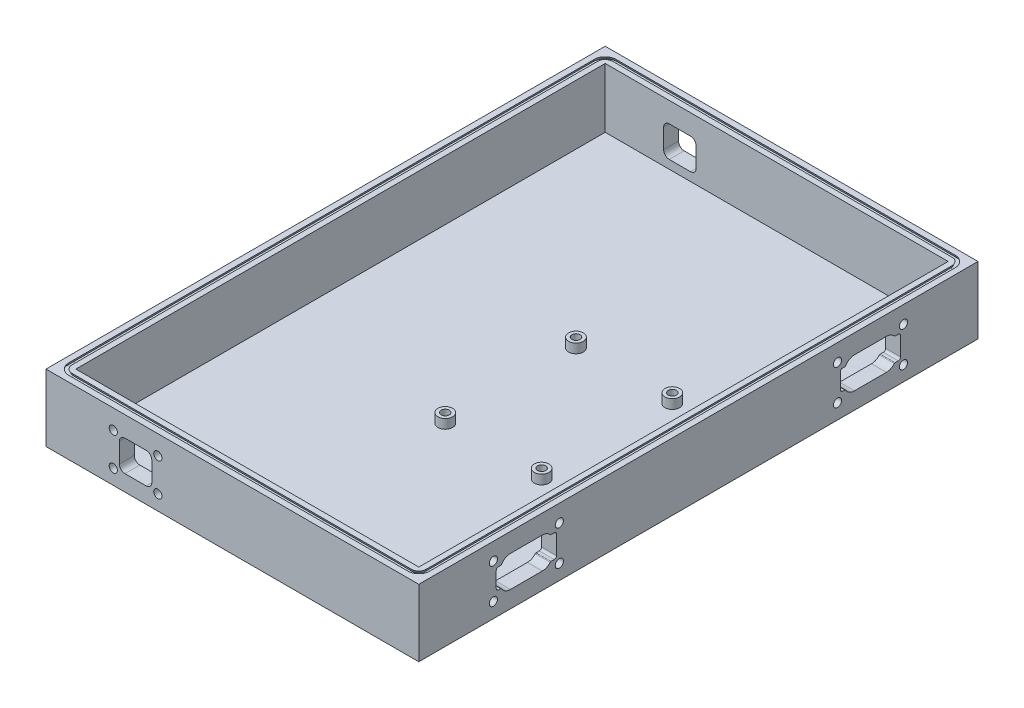
SolidWorks part; units mm, degrees
ref_plane "Front Plane" through (0, 0, 0) normal (0, 0, 1) x (1, 0, 0)
ref_plane "Top Plane" through (0, 0, 0) normal (0, 1, 0) x (1, 0, 0)
ref_plane "Right Plane" through (0, 0, 0) normal (1, 0, 0) x (0, 0, -1)
sketch "Sketch1" plane through (0, 0, 0) normal (0, 1, 0) x (1, 0, 0)
  line L1 (0, 0) -> (254, 0)
  line L2 (0, 0) -> (0, 381)
  line L3 (0, 381) -> (254, 381)
  line L4 (254, 0) -> (254, 381)
  dimension "D1" = 254
  dimension "D2" = 381
extrude "Boss-Extrude1" add sketch "Sketch1" along normal blind 45.72
sketch "12 pin hole" [suppressed] plane through (254, 0, 0) normal (1, 0, 0) x (0, 0, -1)
  line L8 (50.8, 10.16) -> (95.758, 10.16) construction
  line L9 (50.8, 10.16) -> (50.8, 34.036) construction
  line L10 (50.8, 34.036) -> (95.758, 34.036) construction
  line L11 (95.758, 10.16) -> (95.758, 34.036) construction
  line L12 (55.7357, 28.956) -> (54.2925, 28.956)
  line L13 (52.7685, 27.432) -> (52.7685, 16.764)
  line L14 (54.2925, 15.24) -> (55.7357, 15.24)
  line L16 (90.087, 29.972) -> (92.2655, 29.972)
  line L17 (93.7895, 28.448) -> (93.7895, 15.748)
  line L18 (92.2655, 14.224) -> (90.087, 14.224)
  line L21 (62.4205, 25.654) -> (84.1375, 25.654) construction
  line L22 (62.4205, 25.654) -> (62.4205, 18.542) construction
  line L23 (62.4205, 18.542) -> (84.1375, 18.542) construction
  line L24 (84.1375, 25.654) -> (84.1375, 18.542) construction
  line L25 (62.4205, 32.7152) -> (84.1375, 32.7152)
  line L26 (62.4205, 11.4808) -> (84.1375, 11.4808)
  line L27 (52.7685, 22.098) -> (50.8, 22.098) construction
  line L28 (93.7895, 22.098) -> (95.758, 22.098) construction
  arc A4 (62.4205, 32.7152) -> (56.3868, 29.3222) centre (62.4205, 25.654) ccw
  arc A5 (89.5075, 30.2392) -> (84.1375, 32.7152) centre (84.1375, 25.654) ccw
  arc A6 (62.4205, 11.4808) -> (56.3868, 14.8738) centre (62.4205, 18.542) cw
  arc A7 (89.5075, 13.9568) -> (84.1375, 11.4808) centre (84.1375, 18.542) cw
  arc A8 (90.087, 29.972) -> (89.5075, 30.2392) centre (90.087, 30.734) cw
  arc A9 (90.087, 14.224) -> (89.5075, 13.9568) centre (90.087, 13.462) ccw
  arc A10 (55.7357, 15.24) -> (56.3868, 14.8738) centre (55.7357, 14.478) cw
  arc A11 (55.7357, 28.956) -> (56.3868, 29.3222) centre (55.7357, 29.718) ccw
  arc A12 (92.2655, 29.972) -> (93.7895, 28.448) centre (92.2655, 28.448) cw
  arc A13 (93.7895, 15.748) -> (92.2655, 14.224) centre (92.2655, 15.748) cw
  arc A14 (52.7685, 16.764) -> (54.2925, 15.24) centre (54.2925, 16.764) ccw
  arc A15 (54.2925, 28.956) -> (52.7685, 27.432) centre (54.2925, 27.432) ccw
  point P25 (50.8, 22.098)
  point P28 (52.7685, 22.098)
  point P29 (93.7895, 22.098)
  point P34 (62.4205, 22.098)
  point P35 (84.1375, 22.098)
  point P44 (73.279, 10.16)
  point P46 (73.279, 11.4808)
  point P59 (93.7895, 29.972)
  point P62 (93.7895, 14.224)
  point P65 (52.7685, 15.24)
  point P68 (52.7685, 28.956)
  dimension "D4" = 41.021
  dimension "D5" = 15.748
  dimension "D11" = 7.0612
  dimension "D12" = 0.762
  dimension "D13" = 1.524
  dimension "D1" = 44.958
  dimension "D2" = 23.876
  dimension "D8" = 13.716
  dimension "D9" = 21.2344
  dimension "D10" = 21.717
sketch "Sketch2" plane through (0, 45.72, 0) normal (0, 1, 0) x (1, 0, 0)
  line L0 (0, 381) -> (0, 0) construction
  line L1 (10.16, 10.16) -> (243.84, 10.16)
  line L2 (10.16, 10.16) -> (10.16, 370.84)
  line L3 (10.16, 370.84) -> (243.84, 370.84)
  line L4 (243.84, 10.16) -> (243.84, 370.84)
  line L5 (254, 381) -> (0, 381) construction
  line L6 (254, 0) -> (254, 381) construction
  line L7 (0, 0) -> (254, 0) construction
  dimension "D1" = 10.16
  dimension "D2" = 10.16
  dimension "D3" = 10.16
  dimension "D4" = 10.16
extrude "Cut-Extrude1" cut sketch "Sketch2" against normal blind 40.64
ref_plane "Plane1" through (0, 45.72, 0) normal (0, 1, 0) x (1, 0, 0)
sketch "Sketch3" plane through (0, 45.72, 0) normal (0, 1, 0) x (1, 0, 0)
  line L4 (6.35, 11.43) -> (6.35, 369.57)
  line L5 (243.84, 370.84) -> (10.16, 370.84) construction
  line L6 (10.16, 370.84) -> (10.16, 10.16) construction
  line L7 (243.84, 10.16) -> (243.84, 370.84) construction
  line L8 (10.16, 10.16) -> (243.84, 10.16) construction
  line L13 (11.43, 374.65) -> (242.57, 374.65)
  line L14 (247.65, 369.57) -> (247.65, 11.43)
  line L15 (242.57, 6.35) -> (11.43, 6.35)
  arc A0 (6.35, 369.57) -> (11.43, 374.65) centre (11.43, 369.57) cw
  arc A1 (242.57, 374.65) -> (247.65, 369.57) centre (242.57, 369.57) cw
  arc A2 (247.65, 11.43) -> (242.57, 6.35) centre (242.57, 11.43) cw
  arc A3 (11.43, 6.35) -> (6.35, 11.43) centre (11.43, 11.43) cw
  dimension "D5" = 5.08
  dimension "D1" = 3.81
  dimension "D2" = 3.81
  dimension "D3" = 3.81
  dimension "D4" = 3.81
ref_plane "Plane2" through (0, 0, 0) normal (0, 0, 1) x (1, 0, 0)
ref_plane "Plane3" through (0, 0, -15.24) normal (0, 0, 1) x (1, 0, 0)
sketch "Sketch4" plane through (0, 0, -15.24) normal (0, 0, 1) x (1, 0, 0)
  line L0 (4.064, 45.72) -> (3.2724, 43.942)
  line L1 (6.35, 45.72) -> (7.1416, 43.942)
  line L2 (3.2724, 43.942) -> (7.1416, 43.942)
  line L5 (4.064, 45.72) -> (6.35, 45.72)
  dimension "D1" = 1.778
  dimension "D2" = 2.286
  dimension "D3" = 66
  dimension "D4" = 66
sweep "Cut-Sweep2" cut profiles "Sketch4" path "Sketch3"
sketch "Sketch13" plane through (254, 0, 0) normal (1, 0, 0) x (0, 0, -1)
  line L0 (50.8, 10.16) -> (50.8, 0) construction
  line L1 (0, 0) -> (381, 0) construction
  line L2 (50.8, 10.16) -> (0, 10.16) construction
  line L3 (0, 45.72) -> (0, 0) construction
  line L4 (330.2, 0) -> (330.2, 10.16) construction
  line L5 (330.2, 10.16) -> (381, 10.16) construction
  line L6 (381, 45.72) -> (381, 0) construction
  line B0 (50.8, 10.16) -> (95.758, 10.16) construction
  line B1 (50.8, 10.16) -> (50.8, 34.036) construction
  line B2 (50.8, 34.036) -> (95.758, 34.036) construction
  line B3 (95.758, 10.16) -> (95.758, 34.036) construction
  line B4 (55.7357, 28.956) -> (54.2925, 28.956)
  line B5 (52.7685, 27.432) -> (52.7685, 16.764)
  line B6 (54.2925, 15.24) -> (55.7357, 15.24)
  line B7 (90.087, 29.972) -> (92.2655, 29.972)
  line B8 (93.7895, 28.448) -> (93.7895, 15.748)
  line B9 (92.2655, 14.224) -> (90.087, 14.224)
  line B10 (62.4205, 32.7152) -> (84.1375, 32.7152)
  line B11 (62.4205, 11.4808) -> (84.1375, 11.4808)
  arc B12 (62.4205, 32.7152) -> (56.3868, 29.3222) centre (62.4205, 25.654) ccw
  arc B13 (89.5075, 30.2392) -> (84.1375, 32.7152) centre (84.1375, 25.654) ccw
  arc B14 (62.4205, 11.4808) -> (56.3868, 14.8738) centre (62.4205, 18.542) cw
  arc B15 (89.5075, 13.9568) -> (84.1375, 11.4808) centre (84.1375, 18.542) cw
  arc B16 (90.087, 29.972) -> (89.5075, 30.2392) centre (90.087, 30.734) cw
  arc B17 (90.087, 14.224) -> (89.5075, 13.9568) centre (90.087, 13.462) ccw
  arc B18 (55.7357, 15.24) -> (56.3868, 14.8738) centre (55.7357, 14.478) cw
  arc B19 (55.7357, 28.956) -> (56.3868, 29.3222) centre (55.7357, 29.718) ccw
  arc B20 (92.2655, 29.972) -> (93.7895, 28.448) centre (92.2655, 28.448) cw
  arc B21 (93.7895, 15.748) -> (92.2655, 14.224) centre (92.2655, 15.748) cw
  arc B22 (52.7685, 16.764) -> (54.2925, 15.24) centre (54.2925, 16.764) ccw
  arc B23 (54.2925, 28.956) -> (52.7685, 27.432) centre (54.2925, 27.432) ccw
  line B24 (285.242, 10.16) -> (330.2, 10.16) construction
  line B25 (285.242, 10.16) -> (285.242, 34.036) construction
  line B26 (285.242, 34.036) -> (330.2, 34.036) construction
  line B27 (330.2, 10.16) -> (330.2, 34.036) construction
  line B28 (290.1777, 28.956) -> (288.7345, 28.956)
  line B29 (287.2105, 27.432) -> (287.2105, 16.764)
  line B30 (288.7345, 15.24) -> (290.1777, 15.24)
  line B31 (324.529, 29.972) -> (326.7075, 29.972)
  line B32 (328.2315, 28.448) -> (328.2315, 15.748)
  line B33 (326.7075, 14.224) -> (324.529, 14.224)
  line B34 (296.8625, 32.7152) -> (318.5795, 32.7152)
  line B35 (296.8625, 11.4808) -> (318.5795, 11.4808)
  arc B36 (296.8625, 32.7152) -> (290.8288, 29.3222) centre (296.8625, 25.654) ccw
  arc B37 (323.9495, 30.2392) -> (318.5795, 32.7152) centre (318.5795, 25.654) ccw
  arc B38 (296.8625, 11.4808) -> (290.8288, 14.8738) centre (296.8625, 18.542) cw
  arc B39 (323.9495, 13.9568) -> (318.5795, 11.4808) centre (318.5795, 18.542) cw
  arc B40 (324.529, 29.972) -> (323.9495, 30.2392) centre (324.529, 30.734) cw
  arc B41 (324.529, 14.224) -> (323.9495, 13.9568) centre (324.529, 13.462) ccw
  arc B42 (290.1777, 15.24) -> (290.8288, 14.8738) centre (290.1777, 14.478) cw
  arc B43 (290.1777, 28.956) -> (290.8288, 29.3222) centre (290.1777, 29.718) ccw
  arc B44 (326.7075, 29.972) -> (328.2315, 28.448) centre (326.7075, 28.448) cw
  arc B45 (328.2315, 15.748) -> (326.7075, 14.224) centre (326.7075, 15.748) cw
  arc B46 (287.2105, 16.764) -> (288.7345, 15.24) centre (288.7345, 16.764) ccw
  arc B47 (288.7345, 28.956) -> (287.2105, 27.432) centre (288.7345, 27.432) ccw
  dimension "D1" = 50.8
  dimension "D2" = 10.16
sketch_block_instance "Block7-3"
sketch_block "Block7" parameters "D6"=7.0612, "D7"=0.762, "D8"=1.524, "D1"=44.958, "D2"=23.876, "D3"=41.021, "D4"=21.2344, "D5"=21.717
sketch_block_instance "Block7-4"
extrude "Cut-Extrude10" cut sketch "Sketch13" against normal up to next
sketch "12 pin mount" plane through (254, 0, 0) normal (1, 0, 0) x (0, 0, -1)
  circle A0 centre (95.758, 34.036) radius 2.8
  circle A1 centre (95.758, 10.16) radius 2.8
  circle A2 centre (50.8, 10.16) radius 2.8
  circle A3 centre (50.8, 34.036) radius 2.8
  circle A4 centre (285.242, 34.036) radius 2.8
  circle A5 centre (330.2, 34.036) radius 2.8
  circle A6 centre (330.2, 10.16) radius 2.8
  circle A7 centre (285.242, 10.16) radius 2.8
  dimension "D1" = 5.6
extrude "Cut-Extrude3" cut sketch "12 pin mount" against normal blind 5.5
sketch "4 pin connector" plane through (0, 0, 0) normal (0, 0, 1) x (1, 0, 0)
  line L0 (76.2, 0) -> (76.2, 10.16) construction
  line L1 (0, 0) -> (254, 0) construction
  line L2 (76.2, 10.16) -> (254, 10.16) construction
  line L3 (254, 45.72) -> (254, 0) construction
  line L5 (45.847, 32.6136) -> (76.2, 32.6136) construction
  line L6 (45.847, 32.6136) -> (45.847, 10.16) construction
  line L7 (45.847, 10.16) -> (76.2, 10.16) construction
  line L8 (76.2, 32.6136) -> (76.2, 10.16) construction
  line L9 (53.7845, 31.877) -> (68.2625, 31.877)
  line L10 (49.9745, 28.067) -> (49.9745, 14.7066)
  line L11 (53.7845, 10.8966) -> (68.2625, 10.8966)
  line L12 (72.0725, 28.067) -> (72.0725, 14.7066)
  line L13 (61.0235, 10.8966) -> (61.0235, 31.877) construction
  line L14 (49.9745, 21.3868) -> (72.0725, 21.3868) construction
  arc A0 (68.2625, 31.877) -> (72.0725, 28.067) centre (68.2625, 28.067) cw
  arc A1 (68.2625, 10.8966) -> (72.0725, 14.7066) centre (68.2625, 14.7066) ccw
  arc A2 (49.9745, 14.7066) -> (53.7845, 10.8966) centre (53.7845, 14.7066) ccw
  arc A3 (53.7845, 31.877) -> (49.9745, 28.067) centre (53.7845, 28.067) ccw
  point P4 (61.0235, 21.3868)
  point P12 (61.0235, 10.16)
  point P15 (76.2, 21.3868)
  point P20 (72.0725, 31.877)
  point P24 (72.0725, 10.8966)
  point P29 (49.9745, 31.877)
  dimension "D1" = 22.098
  dimension "D7" = 3.81
  dimension "D2" = 22.4536
  dimension "D3" = 30.353
  dimension "D4" = 10.16
  dimension "D5" = 177.8
  dimension "D6" = 20.9804
extrude "Cut-Extrude5" cut sketch "4 pin connector" against normal up to next
extrude "Cut-Extrude6" cut sketch "Sketch5<2>" along normal up to next from surface starting at face at (127, 22.86, -381)
sketch "Sketch5<2>" plane through (0, 0, 0) normal (0, 0, 1) x (1, 0, 0) same geometry as "4 pin connector"
sketch "Sketch6" plane through (0, 0, 0) normal (0, 0, 1) x (1, 0, 0)
  circle A0 centre (76.2, 32.6136) radius 2.8
  circle A1 centre (76.2, 10.16) radius 2.8
  circle A2 centre (45.847, 10.16) radius 2.8
  circle A3 centre (45.847, 32.6136) radius 2.8
  dimension "D1" = 5.6
extrude "Cut-Extrude7" cut sketch "Sketch6" against normal blind 5.5
extrude "Cut-Extrude8" cut sketch "Sketch6<2>" along normal blind 5.5 from surface starting at face at (61.0235, 21.3868, -381)
sketch "Sketch6<2>" plane through (0, 0, 0) normal (0, 0, 1) x (1, 0, 0) same geometry as "Sketch6"
sketch "Sketch7" plane through (0, 5.08, 0) normal (0, 1, 0) x (1, 0, 0)
  line L0 (193.04, 189.1889) -> (243.84, 189.1889) construction
  line L1 (243.84, 10.16) -> (243.84, 370.84) construction
  line L5 (193.04, 144.6739) -> (127.38, 144.6739) construction
  line L6 (193.04, 144.6739) -> (193.04, 233.7039) construction
  line L7 (193.04, 233.7039) -> (127.38, 233.7039) construction
  line L8 (127.38, 144.6739) -> (127.38, 233.7039) construction
  circle A0 centre (127.38, 144.6739) radius 5
  circle A1 centre (193.04, 144.6739) radius 5
  circle A2 centre (193.04, 233.7039) radius 5
  circle A3 centre (127.38, 233.7039) radius 5
  dimension "D1" = 10
  dimension "D2" = 89.03
  dimension "D3" = 65.66
  dimension "D4" = 50.8
sketch "Sketch8" plane through (0, 5.08, 0) normal (0, 1, 0) x (1, 0, 0)
  circle A0 centre (127.38, 233.7039) radius 2.8
  circle A1 centre (193.04, 233.7039) radius 2.8
  circle A2 centre (193.04, 144.6739) radius 2.8
  circle A3 centre (127.38, 144.6739) radius 2.8
  dimension "D1" = 5.6
extrude "Boss-Extrude2" add sketch "Sketch7" along normal blind 6.35
extrude "Cut-Extrude9" cut sketch "Sketch8" against normal blind 5.5 from surface starting at face at (193.04, 11.43, -139.6739)
equation "\"M4 insert  width\"= 5.6mm"
equation "\"M4 insert  depth\"= 5.5mm"
equation "\"depth\"=0.1"
